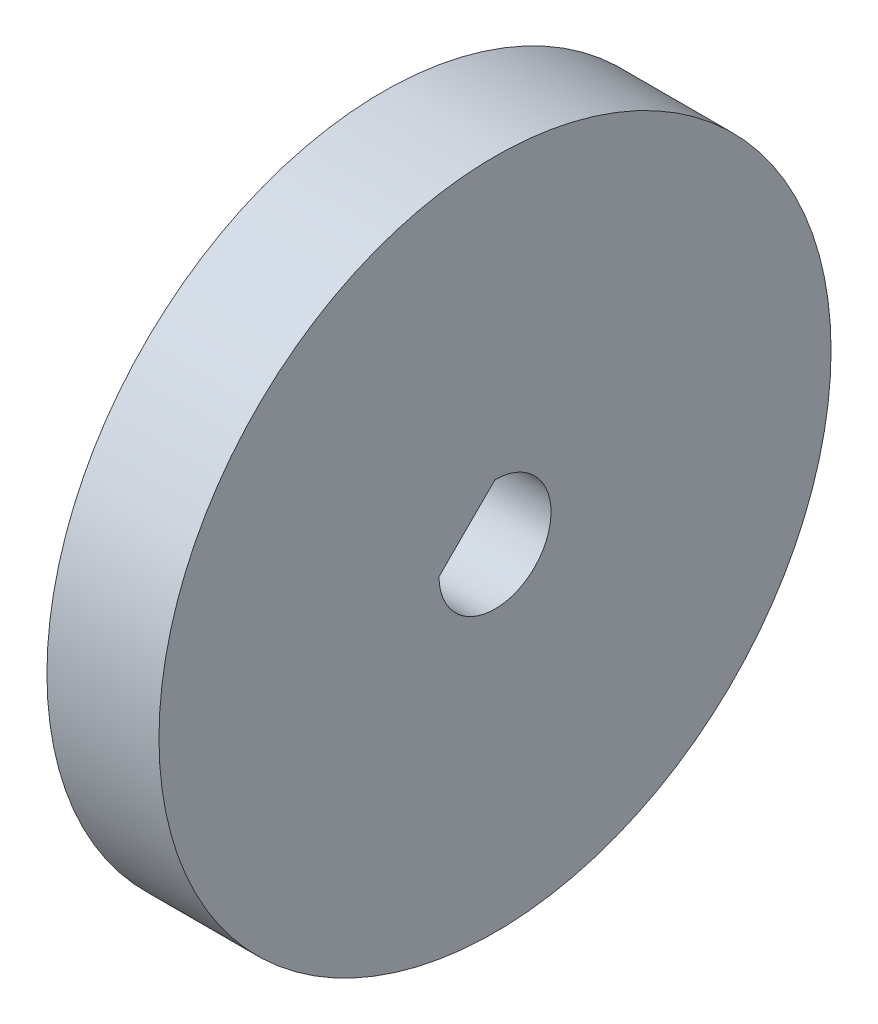
SolidWorks part; units mm, degrees
ref_plane "Front Plane" through (0, 0, 0) normal (0, 0, 1) x (1, 0, 0)
ref_plane "Top Plane" through (0, 0, 0) normal (0, 1, 0) x (1, 0, 0)
ref_plane "Right Plane" through (0, 0, 0) normal (1, 0, 0) x (0, 0, -1)
sketch "Sketch1" plane through (0, 0, 0) normal (1, 0, 0) x (0, 0, -1)
  circle A0 centre (0, 0) radius 19.05
  dimension "D1" = 38.1
extrude "Boss-Extrude1" add sketch "Sketch1" along normal blind 6.35
sketch "Sketch2" plane through (0, 0, 0) normal (-1, 0, 0) x (0, 0, 1)
  line L0 (0, 3.175) -> (3.175, 0)
  arc A0 (0, 3.175) -> (3.175, 0) centre (0, 0) ccw
  dimension "D1" = 6.35
extrude "Cut-Extrude1" cut sketch "Sketch2" against normal up to next
ref_axis "Axis1" through (0, 0, 0) along (1, 0, 0)
